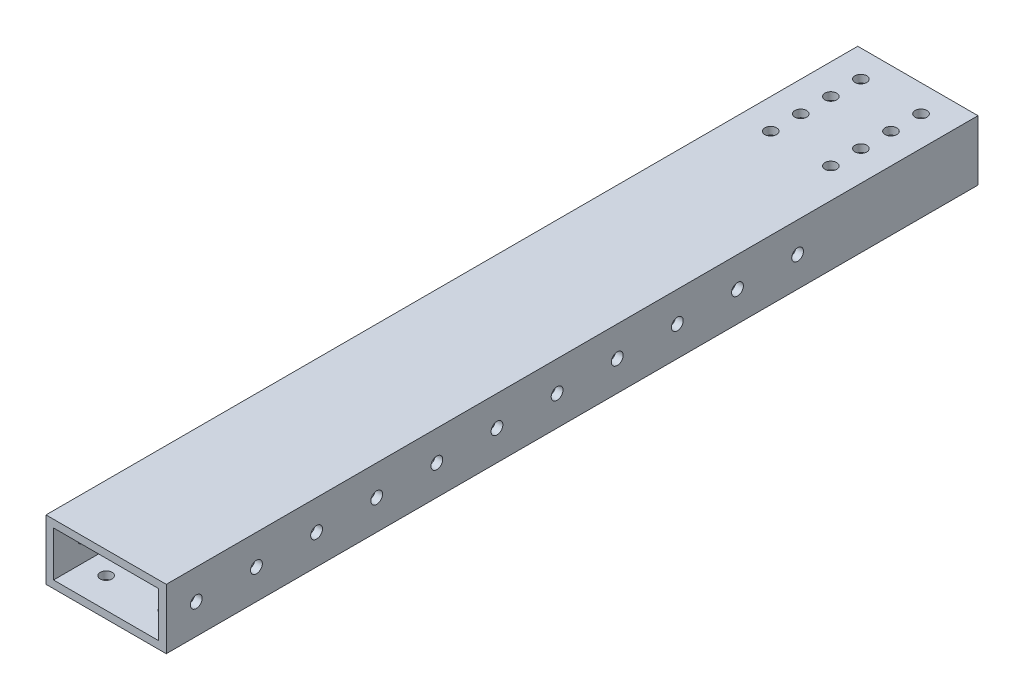
SolidWorks part; units mm, degrees
material "6061-T6 (SS)"
ref_plane "Front Plane" through (0, 0, 0) normal (0, 0, 1) x (1, 0, 0)
ref_plane "Top Plane" through (0, 0, 0) normal (0, 1, 0) x (1, 0, 0)
ref_plane "Right Plane" through (0, 0, 0) normal (1, 0, 0) x (0, 0, -1)
sketch "Sketch1" plane through (0, 0, 0) normal (0, 1, 0) x (1, 0, 0)
  line L1 (0, 0) -> (50.8, 0)
  line L2 (0, 0) -> (0, 342.9)
  line L3 (0, 342.9) -> (50.8, 342.9)
  line L4 (50.8, 0) -> (50.8, 342.9)
  dimension "D1" = 50.8
  dimension "D2" = 342.9
extrude "Boss-Extrude1" add sketch "Sketch1" along normal blind 25.4
shell "Shell1" thickness 3.175 removed face at (25.4, 12.7, -342.9) removed face at (25.4, 12.7, 0)
sketch "Sketch2" plane through (0, 0, 0) normal (-1, 0, 0) x (0, 0, 1)
  line L0 (0, 12.7) -> (-342.9, 12.7) construction
  line L1 (0, 25.4) -> (0, 0) construction
  line L2 (-342.9, 25.4) -> (-342.9, 0) construction
  circle A0 centre (-12.7, 12.7) radius 2.4892
  circle A1 centre (-38.1, 12.7) radius 2.4892
  circle A2 centre (-63.5, 12.7) radius 2.4892
  circle A3 centre (-88.9, 12.7) radius 2.4892
  circle A4 centre (-114.3, 12.7) radius 2.4892
  circle A5 centre (-139.7, 12.7) radius 2.4892
  circle A6 centre (-165.1, 12.7) radius 2.4892
  circle A7 centre (-190.5, 12.7) radius 2.4892
  circle A8 centre (-215.9, 12.7) radius 2.4892
  circle A9 centre (-241.3, 12.7) radius 2.4892
  circle A10 centre (-266.7, 12.7) radius 2.4892
  dimension "D1" = 4.9784
  dimension "D2" = 12.7
  dimension "D3" = 25.4
  dimension "D4" = 11
extrude "Cut-Extrude1" cut sketch "Sketch2" against normal through all
sketch "Sketch3" plane through (0, 25.4, 0) normal (0, 1, 0) x (1, 0, 0)
  circle A0 centre (12.7, 293.4246) radius 2.4892 construction
  circle A1 centre (38.1, 293.4246) radius 2.4892 construction
  circle A2 centre (38.1, 306.1246) radius 2.4892 construction
  circle A3 centre (12.7, 306.1246) radius 2.4892 construction
  circle A4 centre (12.7, 318.8246) radius 2.4892 construction
  circle A5 centre (38.1, 318.8246) radius 2.4892 construction
  circle A6 centre (38.1, 331.5246) radius 2.4892 construction
  circle A7 centre (12.7, 331.5246) radius 2.4892 construction
  circle A8 centre (12.7, 293.4246) radius 2.4892
  circle A9 centre (38.1, 293.4246) radius 2.4892
  circle A10 centre (38.1, 306.1246) radius 2.4892
  circle A11 centre (12.7, 306.1246) radius 2.4892
  circle A12 centre (12.7, 318.8246) radius 2.4892
  circle A13 centre (38.1, 318.8246) radius 2.4892
  circle A14 centre (38.1, 331.5246) radius 2.4892
  circle A15 centre (12.7, 331.5246) radius 2.4892
extrude "Cut-Extrude2" cut sketch "Sketch3" against normal through all
sketch "Sketch4" plane through (0, 0, 0) normal (0, -1, 0) x (1, 0, 0)
  circle A0 centre (38.1, -12.7) radius 2.4892 construction
  circle A2 centre (12.7, -12.7) radius 2.4892 construction
  circle A3 centre (12.7, -25.4) radius 2.4892 construction
  circle A5 centre (38.1, -25.4) radius 2.4892 construction
  circle A6 centre (38.1, -38.1) radius 2.4892 construction
  circle A8 centre (12.7, -38.1) radius 2.4892 construction
  circle A9 centre (12.7, -50.8) radius 2.4892 construction
  circle A11 centre (38.1, -50.8) radius 2.4892 construction
  circle A12 centre (38.1, -63.5) radius 2.4892 construction
  circle A14 centre (12.7, -63.5) radius 2.4892 construction
  circle A15 centre (38.1, -12.7) radius 2.4892
  circle A17 centre (12.7, -12.7) radius 2.4892
  circle A18 centre (12.7, -25.4) radius 2.4892
  circle A20 centre (38.1, -25.4) radius 2.4892
  circle A21 centre (38.1, -38.1) radius 2.4892
  circle A23 centre (12.7, -38.1) radius 2.4892
  circle A24 centre (12.7, -50.8) radius 2.4892
  circle A26 centre (38.1, -50.8) radius 2.4892
  circle A27 centre (38.1, -63.5) radius 2.4892
  circle A29 centre (12.7, -63.5) radius 2.4892
extrude "Cut-Extrude3" cut sketch "Sketch4" against normal up to next
